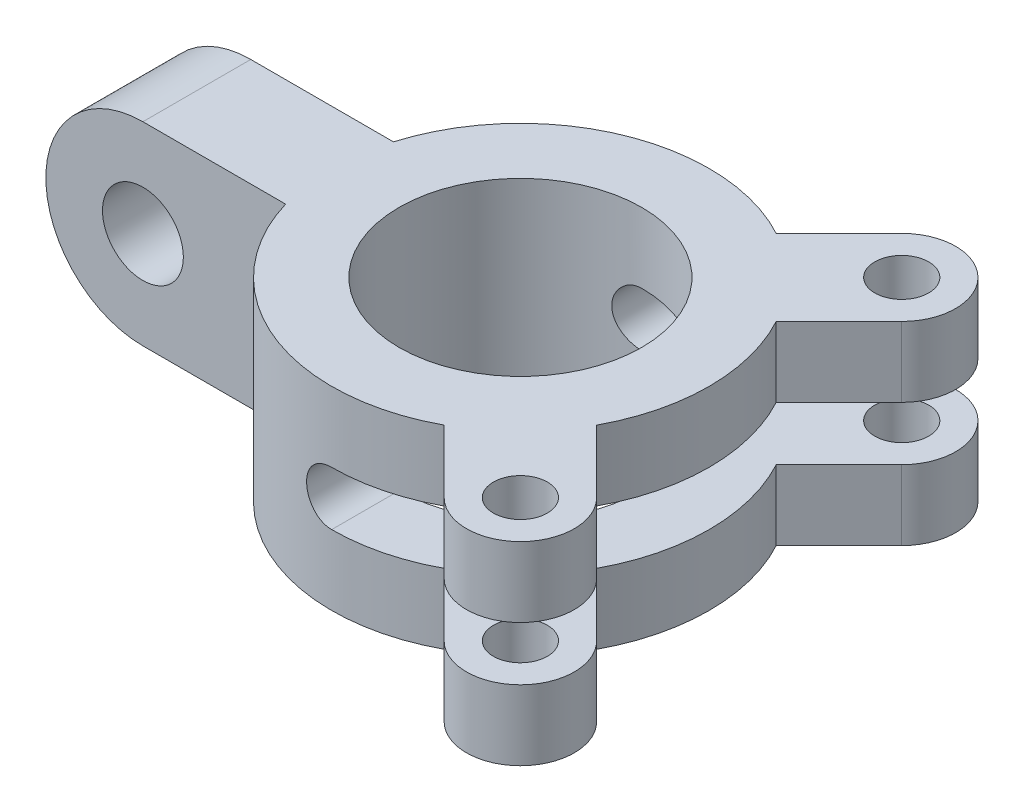
SolidWorks part; units mm, degrees
material "1060 Alloy"
ref_plane "Front Plane" through (0, 0, 0) normal (0, 0, 1) x (1, 0, 0)
ref_plane "Top Plane" through (0, 0, 0) normal (0, 1, 0) x (1, 0, 0)
ref_plane "Right Plane" through (0, 0, 0) normal (1, 0, 0) x (0, 0, -1)
sketch "Sketch1" plane through (0, 0, 0) normal (0, 1, 0) x (1, 0, 0)
  circle A0 centre (0, 0) radius 22.5
  circle A1 centre (0, 0) radius 35
extrude "Boss-Extrude1" add sketch "Sketch1" along normal mid plane 36
sketch "Sketch2" plane through (0, 0, 0) normal (0, 0, 1) x (1, 0, 0)
  line L0 (35, -18) -> (35, 18) construction
  line L1 (35, 5) -> (0, 5)
  line L2 (35, 5) -> (35, -5)
  line L3 (35, -5) -> (0, -5)
  line L4 (0, 5) -> (0, -5)
  circle A0 centre (0, 0) radius 5
  dimension "D1" = 10
  dimension "D3" = 5
extrude "Cut-Extrude1" cut sketch "Sketch2" against normal through all both and the other way through all contours A0 | L3 L4 L1 L2
sketch "Sketch3" plane through (0, 0, 0) normal (0, 1, 0) x (1, 0, 0)
  line L0 (0, 0) -> (69.6999, 0) construction
  line L1 (0, 0) -> (45.5641, -45.5641) construction
  line L2 (28.2843, -42.4264) -> (16.646, -30.7882)
  line L3 (42.4264, -28.2843) -> (30.7882, -16.646)
  circle A0 centre (35.3553, -35.3553) radius 5
  arc A1 (28.2843, -42.4264) -> (42.4264, -28.2843) centre (35.3553, -35.3553) ccw
  circle A2 centre (0, 0) radius 35 construction
  arc A3 (16.646, -30.7882) -> (30.7882, -16.646) centre (0, 0) ccw
  dimension "D2" = 10
  dimension "D3" = 20
  dimension "D4" = 50
extrude "Boss-Extrude2" add sketch "Sketch3" along normal blind 13 from offset 5
mirror "Mirror1" about plane through (0, 0, 0) normal (0, 0, 1) of "Boss-Extrude2"
mirror "Mirror2" about plane through (0, 0, 0) normal (0, 1, 0) of "Mirror1", "Boss-Extrude2"
sketch "Sketch4" plane through (0, 0, 0) normal (0, 0, 1) x (1, 0, 0)
  line L0 (0, 0) -> (-75.8638, 0) construction
  line L1 (-22.5, 18) -> (-22.5, -18) construction
  line L2 (-60, 18) -> (-22.5, 18)
  line L4 (-60, -18) -> (-22.5, -18)
  line L5 (-22.5, 18) -> (-22.5, -18)
  circle A0 centre (-60, 0) radius 7.5
  circle A1 centre (-60, 0) radius 18
  point P13 (0, 0)
  dimension "D2" = 15
  dimension "D3" = 60
extrude "Boss-Extrude4" add sketch "Sketch4" along normal mid plane 20 contours A1 A0 | L5 L0 A1 L4 | L0 L5 L2 A1 region at (-34.5268, 9.8233, 0) region at (-47.6321, -12.3679, 0) region at (-34.5268, -9.8233, 0)
equation "\"A\" = 45"
equation "\"B\" = 70"
equation "\"C\" = 36"
equation "\"D1@Sketch1\"=\"A\""
equation "\"D2@Sketch1\"=\"B\""
equation "\"D1@Boss-Extrude1\"=\"C\""
equation "\"D\"= 45'angle"
equation "\"D1@Sketch3\"=\"D\""
equation "\"D1@Sketch4\"=\"C\""
equation "\"D1@Boss-Extrude2\"=\"Y\""
equation "\"X\"= \"B\" / 2"
equation "\"Y\"= ( \"C\" - 10 ) / 2"
equation "\"D2@Sketch2\"=\"X\""
